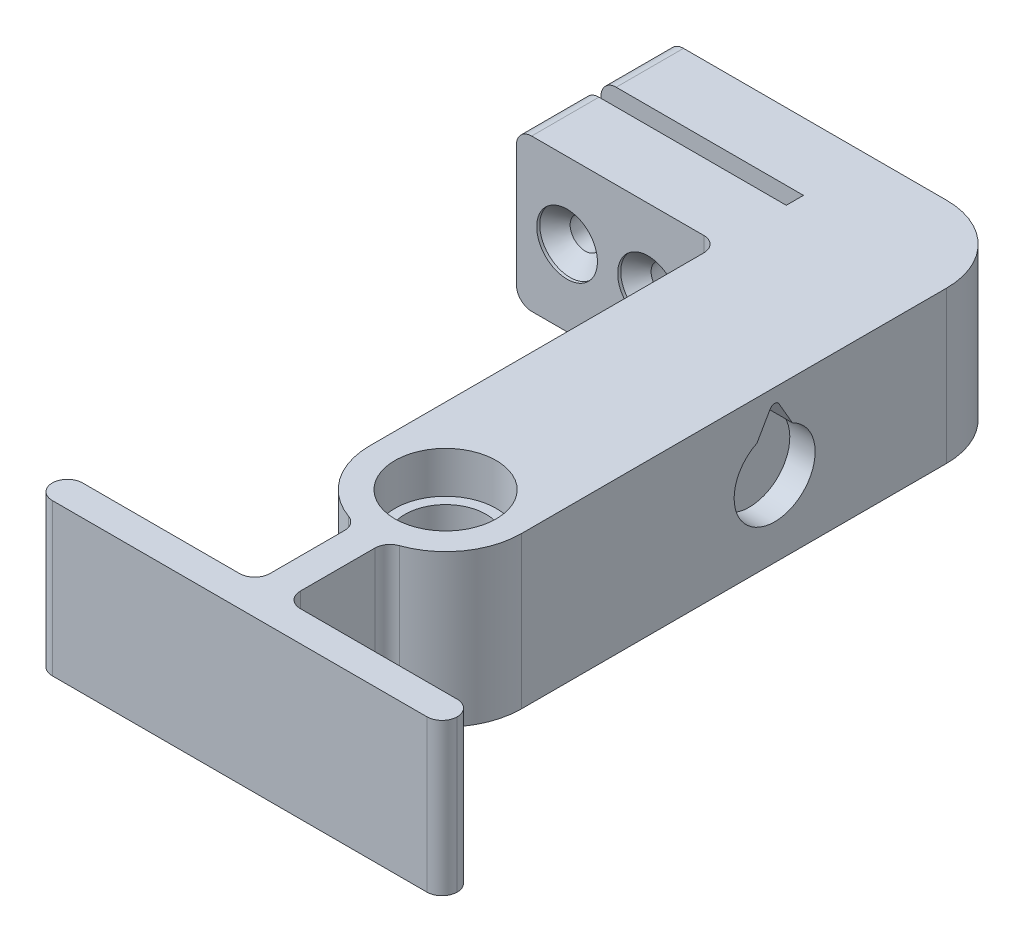
SolidWorks part; units mm, degrees
ref_plane "Front Plane" through (0, 0, 0) normal (0, 0, 1) x (1, 0, 0)
ref_plane "Top Plane" through (0, 0, 0) normal (0, 1, 0) x (1, 0, 0)
ref_plane "Right Plane" through (0, 0, 0) normal (1, 0, 0) x (0, 0, -1)
sketch "Sketch1" plane through (0, 0, 0) normal (0, 1, 0) x (1, 0, 0)
  line L0 (0, 21) -> (0, -21) construction
  line L1 (-7.5, 21) -> (7.5, 21)
  line L2 (-7.5, 21) -> (-7.5, -21)
  line L3 (-7.5, -21) -> (7.5, -21)
  line L4 (7.5, 21) -> (7.5, -21)
  line L5 (-7.5, 21) -> (7.5, -21) construction
  line L6 (-7.5, -21) -> (7.5, 21) construction
  circle A0 centre (0, -13.5) radius 4
  circle A1 centre (0, -13.5) radius 7.5
  point P0 (0, 0)
  dimension "D1" = 8
  dimension "D2" = 15
  dimension "D4" = 42
extrude "Boss-Extrude1" add sketch "Sketch1" along normal mid plane 15 contours L2 | L4 | A1 L4 L1 L2 | A1 A0 | L3 region at (0, 0, -6.6463) region at (0, 0, 6.2121)
sketch "Sketch2" plane through (0, 7.5, 0) normal (0, 1, 0) x (1, 0, 0)
  circle A0 centre (0, -13.5) radius 5
  dimension "D1" = 10
extrude "Cut-Extrude1" cut sketch "Sketch2" against normal blind 4.1
mirror "Mirror1" about plane through (0, 0, 0) normal (0, 1, 0) of "Cut-Extrude1"
sketch "Sketch12" plane through (0, -3.4, 0) normal (0, -1, 0) x (1, 0, 0)
  circle A0 centre (0, 13.5) radius 4 construction
  circle A1 centre (0, 13.5) radius 5
  circle A2 centre (0, 13.5) radius 5
  circle A3 centre (0, 13.5) radius 4
  dimension "D1" = 0
extrude "Cut-Extrude10" cut sketch "Sketch12" against normal blind 1
sketch "Sketch4" plane through (7.5, 0, 0) normal (1, 0, 0) x (0, 0, -1)
  line L0 (-3.1918, 0) -> (3.917, 0) construction
  line L1 (9.75, 3.5969) -> (13.25, 3.5969) construction
  line L2 (-8.5, 7.5) -> (-18.5, 7.5) construction
  line L3 (-8.5, 7.5) -> (-18.5, 7.5)
  line L4 (-13.5, 7.5) -> (-13.5, -7.5) construction
  line L5 (21, -7.5) -> (-13.5, -7.5) construction
  line L6 (11.5, 0) -> (11.5, 7.5) construction
  line L9 (21, 7.5) -> (-13.5, 7.5) construction
  line L10 (11.5, 6.628) -> (9.75, 3.5969)
  line L11 (11.5, 6.628) -> (13.25, 3.5969)
  circle A1 centre (11.5, 0) radius 4
  circle A3 centre (11.5, 5.628) radius 0.5
  dimension "D1" = 25
  dimension "D2" = 8
  dimension "D5" = 1
  dimension "D4" = 3.5
extrude "Cut-Extrude3" cut sketch "Sketch4" against normal blind 2.5 contours A1 | A1 L11 L10 | A3 region at (7.5, 4.5253, -11.5) region at (7.5, 5.628, -11.5) region at (7.5, 0, -11.5)
mirror "Mirror2" about plane through (0, 0, 0) normal (1, 0, 0) of "Cut-Extrude3"
sketch "Sketch18" plane through (0, -7.5, 0) normal (0, -1, 0) x (1, 0, 0)
  line L0 (0, -41.3409) -> (0, 22.3101) construction
  line L4 (7.5, -3.75) -> (-7.5, -3.75) construction
  line L5 (-27.5, -21) -> (-7.5, -21)
  line L6 (7.5, -28.5) -> (7.5, -21)
  line L7 (7.5, -21) -> (7.5, 13.5) construction
  line L8 (-7.5, -21) -> (7.5, -21)
  line L9 (-7.5, -21) -> (-7.5, 13.5) construction
  line L10 (0, -21) -> (0, -36) construction
  line L11 (0, -36) -> (-27.5, -36)
  line L13 (-27.5, -21) -> (-27.5, -36)
  circle A1 centre (0, -28.5) radius 7.5
  line M10 (-7.5, -21) -> (7.5, -21)
  dimension "D1" = 20
extrude "Boss-Extrude3" add sketch "Sketch18" against normal up to surface (15 mm away) contours A1 L6 L8 | A1 M10 | A1 | A1 L13 L11 region at (-16.6304, -7.5, -28.5) region at (5.8247, -7.5, -22.6753) region at (0, -7.5, -28.5) up to face at (0, 7.5, 18.5)
sketch "Sketch7" plane through (0, 7.5, 0) normal (0, 1, 0) x (1, 0, 0)
  line L0 (-27.5, 28.5) -> (7.5, 28.5) construction
  line L8 (7.5, 28.5) -> (7.5, -13.5) construction
  line L9 (-27.5, 27.65) -> (-7.5, 27.65)
  line L10 (-27.5, 27.65) -> (-27.5, 29.35)
  line L11 (-7.5, 27.65) -> (-7.5, 29.35)
  line L12 (-27.5, 29.35) -> (-7.5, 29.35)
  line L13 (-27.5, 27.65) -> (-7.5, 29.35) construction
  line L14 (-7.5, 27.65) -> (-27.5, 29.35) construction
  line L15 (-27.5, 21) -> (-27.5, 36) construction
  point P8 (-17.5, 28.5)
  dimension "D1" = 20
  dimension "D2" = 1.7
extrude "Cut-Extrude7" cut sketch "Sketch7" against normal up to next
sketch "Sketch8" plane through (-40.2452, 0, -36) normal (0, 0, 1) x (1, 0, 0)
  line L5 (12.7452, 0) -> (40.2452, 0) construction
  line L8 (12.7452, 7.5) -> (12.7452, -7.5) construction
  line L9 (40.2452, 7.5) -> (40.2452, -7.5) construction
  circle A2 centre (17.7452, 0) radius 1.5
  circle A3 centre (25.7452, 0) radius 1.5
  dimension "D2" = 5
  dimension "D3" = 3
  dimension "D1" = 8
extrude "Cut-Extrude8" cut sketch "Sketch8" along normal up to surface (15 mm away) contours A3 | A2
hole_wizard "CSK for M3 Flat Head Machine Screw1" positions "Sketch9" profile "Sketch10" countersink size "M3" standard "ANSI Metric"
sketch "Sketch9" plane through (-83.1458, 0, -21) normal (0, 0, 1) x (1, 0, 0)
  point P6 (60.6458, 0)
  point P9 (68.6458, 0)
sketch "Sketch10" plane through (-22.5, 0, -21) normal (1, 0, 0) x (0, -1, 0)
  line L0 (0, 0) -> (0, 5.9013)
  line L1 (0, 5.9013) -> (1.5, 5)
  line L2 (1.5, 5) -> (1.5, 1.8)
  line L3 (1.5, 1.8) -> (3, 0.3)
  line L4 (3, 0.3) -> (3, 0)
  line L6 (3, 0) -> (0, 0)
  line L7 (-1.5, 1.8) -> (-3, 0.3) construction
  line L10 (0, 5.9013) -> (-1.5, 5) construction
  line L11 (0, -6.35) -> (0, 107.95) construction
  dimension "Hole Dia." = 3
  dimension "Hole Depth" = 5
  dimension "C'Sink Dia." = 6
  dimension "C'Sink Angle" = 90
  dimension "Drill Angle" = 118
  dimension "Head Clearance" = 0.3
sketch "Sketch11" plane through (15, 0, -36) normal (0, 0, 1) x (1, 0, 0)
  line L0 (-29.5, 0) -> (-37.5, 0) construction
  line L1 (-26.0359, 0) -> (-27.7679, 3)
  line L2 (-27.7679, 3) -> (-31.2321, 3)
  line L3 (-31.2321, 3) -> (-32.9641, 0)
  line L4 (-32.9641, 0) -> (-31.2321, -3)
  line L5 (-31.2321, -3) -> (-27.7679, -3)
  line L6 (-27.7679, -3) -> (-26.0359, 0)
  line L7 (-33.5, 0) -> (-33.5, 7.5) construction
  line L9 (-40.9641, 0) -> (-39.2321, 3)
  line L10 (-39.2321, -3) -> (-40.9641, 0)
  line L11 (-35.7679, -3) -> (-39.2321, -3)
  line L12 (-34.0359, 0) -> (-35.7679, -3)
  line L13 (-35.7679, 3) -> (-34.0359, 0)
  line L14 (-39.2321, 3) -> (-35.7679, 3)
  line L15 (-42.5, 7.5) -> (-22.5, 7.5) construction
  circle A0 centre (-29.5, 0) radius 3 construction
  point P11 (-33.5, 7.5)
  dimension "D1" = 6
extrude "Cut-Extrude9" cut sketch "Sketch11" along normal blind 3
sketch "Sketch13" plane through (-44.6536, 0, -29.35) normal (0, 0, 1) x (1, 0, 0)
  line L0 (37.1536, -7.5) -> (37.1536, 7.5) construction
  line L2 (37.1536, -7.5) -> (37.1536, 7.5)
  line L3 (37.1536, 0) -> (44.6536, 0) construction
  line L4 (44.6536, 7.5) -> (44.6536, -7.5) construction
  line L5 (37.1536, 7.5) -> (44.6536, 0)
  line L6 (37.1536, -7.5) -> (44.6536, 0)
  dimension "D1" = 45
extrude "Cut-Extrude11" cut sketch "Sketch13" along normal up to surface (1.7 mm away) contours L5 L6 L2 up to face at (-13, 0, -27.65)
sketch "Sketch16" plane through (0, -7.5, 0) normal (0, -1, 0) x (1, 0, 0)
  line L0 (0, 42.718) -> (0, -5.4521) construction
  line L2 (-1.5, 30.8485) -> (1.5, 30.8485)
  line L3 (-1.5, 30.8485) -> (-1.5, 20.8485)
  line L4 (-1.5, 20.8485) -> (1.5, 20.8485)
  line L5 (1.5, 30.8485) -> (1.5, 20.8485)
  line L6 (-1.5, 30.8485) -> (1.5, 20.8485) construction
  line L7 (-1.5, 20.8485) -> (1.5, 30.8485) construction
  line L8 (-20, 33.8485) -> (20, 33.8485)
  line L9 (-20, 33.8485) -> (-20, 30.8485)
  line L10 (-20, 30.8485) -> (20, 30.8485)
  line L11 (20, 33.8485) -> (20, 30.8485)
  line L12 (-20, 33.8485) -> (20, 30.8485) construction
  line L13 (-20, 30.8485) -> (20, 33.8485) construction
  arc A0 (7.5, 13.5) -> (-7.5, 13.5) centre (0, 13.5) ccw construction
  point P1 (0, 25.8485)
  point P11 (0, 32.3485)
  arc M14 (7.5, 13.5) -> (-7.5, 13.5) centre (0, 13.5) ccw
  dimension "D1" = 3
  dimension "D2" = 10
  dimension "D3" = 40
extrude "Boss-Extrude2" add sketch "Sketch16" against normal up to surface (15 mm away) contours L5 L2 L3 M14 | L11 L8 L9 L10 L2 region at (0, -7.5, 32.3485) region at (0, -7.5, 25.899) up to face at (-11.2224, 7.5, -20.323)
fillet "Fillet8" radius 1.5 13 edges at (20, 0, 30.8485) (20, 0, 33.8485) (-20, 0, 33.8485) (-20, 0, 30.8485) (-1.5, 0, 30.8485) (-1.5, 0, 20.8485) (1.5, 0, 20.8485) (1.5, 0, 30.8485) (-27.5, -7.5, -24.325) (-27.5, -7.5, -32.675) (-27.5, 7.5, -32.675) (-27.5, 7.5, -24.325) (-7.5, 0, -21)
